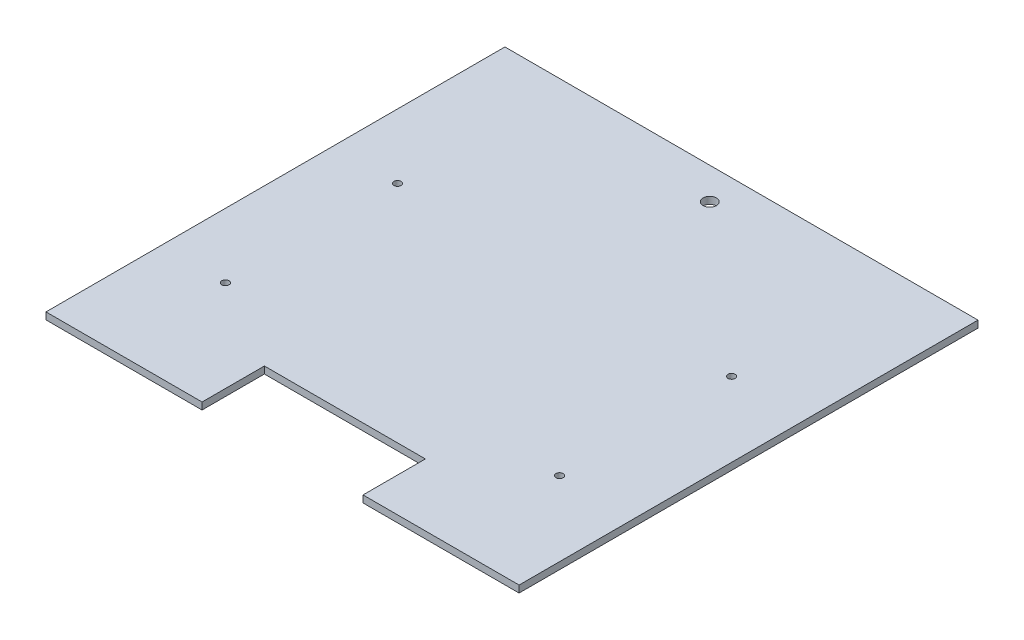
SolidWorks part; units mm, degrees
ref_plane "Front Plane" through (0, 0, 0) normal (0, 0, 1) x (1, 0, 0)
ref_plane "Top Plane" through (0, 0, 0) normal (0, 1, 0) x (1, 0, 0)
ref_plane "Right Plane" through (0, 0, 0) normal (1, 0, 0) x (0, 0, -1)
sketch "Sketch1" plane through (0, 0, 0) normal (0, 1, 0) x (1, 0, 0)
  line L1 (-94.869, -92.025) -> (94.869, -92.025)
  line L2 (-94.869, -92.025) -> (-94.869, 92.025)
  line L3 (-94.869, 92.025) -> (94.869, 92.025)
  line L4 (94.869, -92.025) -> (94.869, 92.025)
  line L5 (-94.869, -92.025) -> (94.869, 92.025) construction
  line L6 (-94.869, 92.025) -> (94.869, -92.025) construction
  point P0 (0, 0)
  dimension "D1" = 189.738
  dimension "D2" = 184.05
extrude "Boss-Extrude1" add sketch "Sketch1" along normal blind 2.794
sketch "Sketch2" plane through (0, 2.794, 0) normal (0, 1, 0) x (1, 0, 0)
  line L2 (94.869, 92.025) -> (-94.869, 92.025) construction
  circle A0 centre (0, 79.325) radius 2.6797
  point P4 (0, 92.025)
  dimension "D1" = 5.3594
  dimension "D2" = 12.7
extrude "Cut-Extrude1" cut sketch "Sketch2" against normal through all
sketch "Sketch3" plane through (0, 2.794, 0) normal (0, 1, 0) x (1, 0, 0)
  line L0 (0, -92.025) -> (-32.28, -92.025)
  line L1 (-94.869, -92.025) -> (94.869, -92.025) construction
  line L2 (-32.28, -92.025) -> (-32.28, -67.025)
  line L3 (-32.28, -67.025) -> (32.28, -67.025)
  line L4 (32.28, -67.025) -> (32.28, -92.025)
  line L5 (32.28, -92.025) -> (0, -92.025)
  point P5 (0, -67.025)
  dimension "D1" = 64.56
  dimension "D3" = 25
extrude "Cut-Extrude2" cut sketch "Sketch3" against normal through all
sketch "Sketch4" plane through (0, 2.794, 0) normal (0, 1, 0) x (1, 0, 0)
  line L1 (-80, -53.925) -> (80, -53.925) construction
  line L2 (-80, -53.925) -> (-80, 36.075) construction
  line L3 (-80, 36.075) -> (80, 36.075) construction
  line L4 (80, -53.925) -> (80, 36.075) construction
  line L7 (-94.869, -92.025) -> (-32.28, -92.025) construction
  circle A1 centre (-69, -45.925) radius 1.45
  circle A2 centre (-69, 23.075) radius 1.45
  circle A4 centre (65, 23.075) radius 1.45
  circle A5 centre (65, -45.925) radius 1.45
  point P6 (0, -53.925)
  dimension "D5" = 2.9
  dimension "D8" = 11
  dimension "D9" = 8
  dimension "D12" = 77
  dimension "D13" = 11
  dimension "D14" = 145
  dimension "D15" = 8
  dimension "D16" = 145
  dimension "D17" = 77
  dimension "D2" = 90
  dimension "D3" = 160
  dimension "D4" = 38.1
extrude "Cut-Extrude3" cut sketch "Sketch4" against normal through all contours A2 | A1 | A5 | A4
